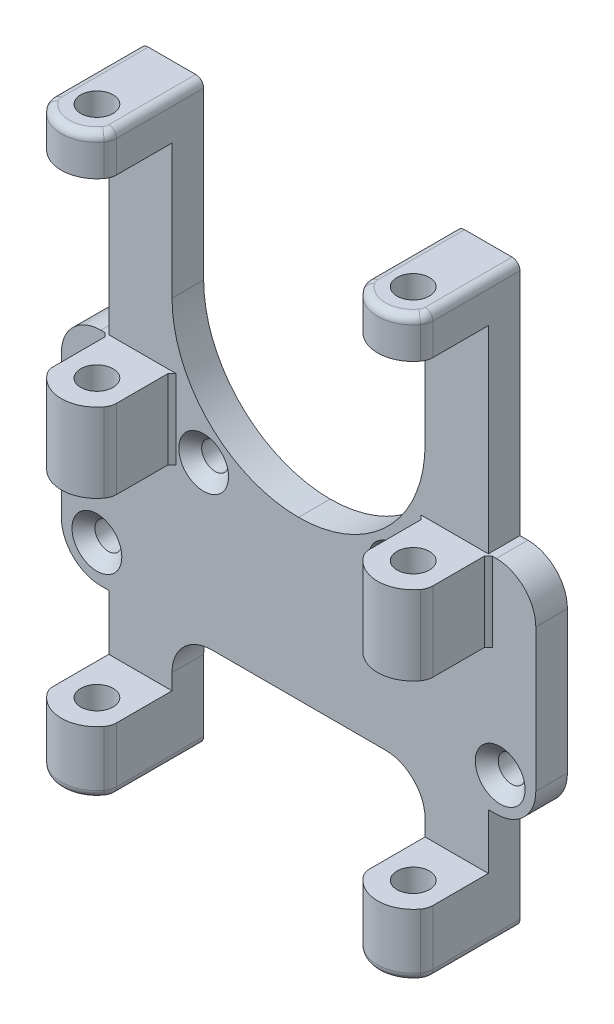
SolidWorks part; units mm, degrees
ref_plane "Front Plane" through (0, 0, 0) normal (0, 0, 1) x (1, 0, 0)
ref_plane "Top Plane" through (0, 0, 0) normal (0, 1, 0) x (1, 0, 0)
ref_plane "Right Plane" through (0, 0, 0) normal (1, 0, 0) x (0, 0, -1)
sketch "Sketch1" plane through (0, 0, 0) normal (0, 0, 1) x (1, 0, 0)
  line L0 (-30, 14) -> (30, -14) construction
  line L1 (-30, 14) -> (-16, 14)
  line L2 (-30, 14) -> (-30, -14)
  line L3 (-30, -14) -> (30, -14)
  line L4 (30, 14) -> (30, -14)
  line L5 (0, 0) -> (0, 36.8289) construction
  line L7 (16, 14) -> (30, 14)
  arc A3 (-16, 14) -> (16, 14) centre (0, 26) ccw
  point P4 (0, 0)
  point P5 (0, 0)
  point P8 (0, 6)
  dimension "D3" = 14
  dimension "D4" = 32
  dimension "D1" = 60
  dimension "D2" = 28
  dimension "D5" = 8
  dimension "D6" = 20
extrude "Boss-Extrude1" add sketch "Sketch1" along normal mid plane 4
sketch "Sketch2" plane through (0, 0, -2) normal (0, 0, -1) x (-1, 0, 0)
  line L5 (0, 0) -> (0, 55.0176) construction
  line L6 (16, 14) -> (30, 14) construction
  line L11 (-24, 44) -> (-16, 44)
  line L12 (-24, 44) -> (-24, -29)
  line L13 (-24, -29) -> (-16, -29)
  line L14 (-16, 44) -> (-16, -29)
  line L15 (16, 44) -> (24, 44)
  line L16 (16, 44) -> (16, -29)
  line L17 (16, -29) -> (24, -29)
  line L18 (24, 44) -> (24, -29)
  dimension "D1" = 48
  dimension "D2" = 8
  dimension "D3" = 73
  dimension "D4" = 30
extrude "Boss-Extrude2" add sketch "Sketch2" against normal up to surface (4 mm away) up to face at (0, 3.3333, 2)
hole_wizard "CSK for M3 Flat Countersunk Head Screw1" positions "Sketch3" profile "Sketch4" countersink size "M3" standard "JIS"
sketch "Sketch3" plane through (0, 0, 2) normal (0, 0, 1) x (1, 0, 0)
  line L1 (0, 0) -> (0, -19.5907) construction
  line L4 (30, -14) -> (30, 14) construction
  line L5 (24, -14) -> (30, -14) construction
  line L7 (30, 14) -> (24, 14) construction
  point P2 (25.5, -9.5)
  point P4 (-25.5, -9.5)
  point P25 (-12, 6)
  point P27 (12, 6)
  point P32 (0, 0)
  dimension "D2" = 4.5
  dimension "D3" = 4.5
  dimension "D4" = 8
  dimension "D5" = 24
sketch "Sketch4" plane through (25.5, -9.5, 2) normal (1, 0, 0) x (0, -1, 0)
  line L0 (0, 0) -> (0, 11.0215)
  line L1 (0, 11.0215) -> (1.7, 10)
  line L2 (1.7, 10) -> (1.7, 1.45)
  line L3 (1.7, 1.45) -> (3.15, 0)
  line L5 (3.15, 0) -> (0, 0)
  line L6 (-1.7, 1.45) -> (-3.15, 0) construction
  line L10 (0, 11.0215) -> (-1.7, 10) construction
  line L11 (0, -6.35) -> (0, 107.95) construction
  dimension "Hole Dia." = 3.4
  dimension "Hole Depth" = 10
  dimension "Near C'Sink Dia." = 6.3
  dimension "Near C'Sink Angle" = 90
  dimension "Drill Angle" = 118
sketch "Sketch5" plane through (0, -29, 0) normal (0, -1, 0) x (-1, 0, 0)
  line L0 (0, 0) -> (0, -18.7503) construction
  line L1 (-16, -2) -> (-24, -2) construction
  line L2 (24, -2) -> (24, -9.5616)
  line L3 (24, -2) -> (16, -2)
  line L4 (24, -2) -> (16, -2) construction
  line L5 (16, -2) -> (16, -9.5616)
  line L6 (-16, -9.5616) -> (-16, -2)
  line L7 (-16, -2) -> (-24, -2)
  line L8 (-24, -2) -> (-24, -9.5616)
  line L9 (-20, -7.5) -> (-20, -16.0423) construction
  circle A1 centre (20, -7.5) radius 2.05
  circle A2 centre (-20, -7.5) radius 2.05
  arc A3 (-24, -9.5616) -> (-16, -9.5616) centre (-20, -7.5) ccw
  arc A4 (16, -9.5616) -> (24, -9.5616) centre (20, -7.5) ccw
  dimension "D1" = 40
  dimension "D2" = 9
  dimension "D3" = 4.1
  dimension "D4" = 5.5
extrude "Boss-Extrude3" add sketch "Sketch5" against normal blind 8
sketch "Sketch6" plane through (0, 14, 0) normal (0, 1, 0) x (1, 0, 0)
  line L3 (24, -2) -> (16, -2)
  line L4 (24, -9.5616) -> (24, -2)
  line L5 (16, -2) -> (16, -9.5616)
  line L6 (24, -2) -> (16, -2)
  line L7 (24, -9.5616) -> (24, -2)
  line L8 (16, -2) -> (16, -9.5616)
  line L9 (-24, -2) -> (-24, -9.5616)
  line L10 (-16, -2) -> (-24, -2)
  line L11 (-16, -9.5616) -> (-16, -2)
  line L12 (-24, -2) -> (-24, -9.5616)
  line L13 (-16, -2) -> (-24, -2)
  line L14 (-16, -9.5616) -> (-16, -2)
  circle A1 centre (20, -7.5) radius 2.05
  circle A2 centre (20, -7.5) radius 2.05
  circle A3 centre (-20, -7.5) radius 2.05
  circle A4 centre (-20, -7.5) radius 2.05
  arc A5 (16, -9.5616) -> (24, -9.5616) centre (20, -7.5) ccw
  arc A7 (-24, -9.5616) -> (-16, -9.5616) centre (-20, -7.5) ccw
  arc A11 (16, -9.5616) -> (24, -9.5616) centre (20, -7.5) ccw construction
  arc A16 (16, -9.5616) -> (24, -9.5616) centre (20, -7.5) ccw
  arc A17 (-24, -9.5616) -> (-16, -9.5616) centre (-20, -7.5) ccw construction
  arc A18 (-24, -9.5616) -> (-16, -9.5616) centre (-20, -7.5) ccw
  dimension "D1" = 0
  dimension "D2" = 0
  dimension "D3" = 0
  dimension "D4" = 0
extrude "Boss-Extrude4" add sketch "Sketch6" against normal blind 10
sketch "Sketch7" plane through (0, 44, 0) normal (0, 1, 0) x (1, 0, 0)
  line L3 (24, -2) -> (16, -2)
  line L4 (24, -9.5616) -> (24, -2)
  line L5 (16, -2) -> (16, -9.5616)
  line L6 (24, -2) -> (16, -2)
  line L7 (24, -9.5616) -> (24, -2)
  line L8 (16, -2) -> (16, -9.5616)
  line L9 (-24, -2) -> (-24, -9.5616)
  line L10 (-16, -2) -> (-24, -2)
  line L11 (-16, -9.5616) -> (-16, -2)
  line L12 (-24, -2) -> (-24, -9.5616)
  line L13 (-16, -2) -> (-24, -2)
  line L14 (-16, -9.5616) -> (-16, -2)
  circle A1 centre (20, -7.5) radius 2.05
  circle A2 centre (20, -7.5) radius 2.05
  circle A3 centre (-20, -7.5) radius 2.05
  circle A4 centre (-20, -7.5) radius 2.05
  arc A5 (16, -9.5616) -> (24, -9.5616) centre (20, -7.5) ccw
  arc A6 (16, -9.5616) -> (24, -9.5616) centre (20, -7.5) ccw
  arc A7 (-24, -9.5616) -> (-16, -9.5616) centre (-20, -7.5) ccw
  arc A9 (-24, -9.5616) -> (-16, -9.5616) centre (-20, -7.5) ccw
  dimension "D1" = 0
  dimension "D2" = 0
  dimension "D3" = 0
  dimension "D4" = 0
extrude "Boss-Extrude5" add sketch "Sketch7" against normal blind 5
hole_wizard "CSK for M3 Flat Countersunk Head Screw2" positions "Sketch11" profile "Sketch12" countersink size "M3" standard "JIS" end condition up to next
sketch "Sketch11" plane through (0, 0, -2) normal (0, 0, -1) x (-1, 0, 0)
  line L2 (0, 0) -> (0, 26.2558) construction
  line L4 (24, 14) -> (30, 14) construction
  point P0 (-20, 9)
  point P2 (20, 9)
  dimension "D1" = 40
  dimension "D2" = 5
sketch "Sketch12" plane through (20, 9, -2) normal (1, 0, 0) x (0, 1, 0)
  line L0 (0, 0) -> (0, 7.45)
  line L1 (0, 7.45) -> (1.7, 7.45)
  line L2 (1.7, 7.45) -> (1.7, 2.45)
  line L3 (1.7, 2.45) -> (4.15, 0)
  line L5 (4.15, 0) -> (0, 0)
  line L6 (-1.7, 2.45) -> (-4.15, 0) construction
  line L11 (0, -6.35) -> (0, 107.95) construction
  dimension "Thru Hole Dia." = 3.4
  dimension "Thru Hole Depth" = 7.45
  dimension "Near C'Sink Dia." = 8.3
  dimension "Near C'Sink Angle" = 90
sketch "Sketch13" plane through (0, 0, -2) normal (0, 0, -1) x (-1, 0, 0)
  circle A0 centre (-20, 9) radius 2.1
  circle A1 centre (20, 9) radius 2.1
  dimension "D1" = 4.2
extrude "Cut-Extrude1" cut sketch "Sketch13" against normal blind 5
fillet "Fillet1" radius 5 6 edges at (30, -14, 0) (-30, -14, 0) (-30, 14, 0) (30, 14, 0) (16, -14, 0) (-16, -14, 0)
fillet "Fillet2" radius 16 2 edges at (16, 14, 0) (-16, 14, 0)
fillet "Fillet3" radius 2 12 edges at (16, -25, 9.5616) (24, -25, 9.5616) (-24, 41.5, 9.5616) (-16, 41.5, 9.5616) (24, 41.5, 9.5616) (16, 41.5, 9.5616) (16, 9, 9.5616) (24, 9, 9.5616) (-16, 9, 9.5616) (-24, 9, 9.5616) (-24, -25, 9.5616) (-16, -25, 9.5616)
fillet "Fillet4" radius 1 20 edges at (16, -29, 3.5) (-16, -29, 3.5) (16, 44, 3.5) (-16, 44, 3.5) (24, 44, 3.5) (-24, 44, 3.5) (-24, -29, 3.5) (24, -29, 3.5) (23.8974, -29, 9.6325) (20, -29, 12) (16.1026, -29, 9.6325) (-23.8974, -29, 9.6325) (-20, -29, 12) (-16.1026, -29, 9.6325) (23.8974, 44, 9.6325) (20, 44, 12) (16.1026, 44, 9.6325) (-23.8974, 44, 9.6325) (-20, 44, 12) (-16.1026, 44, 9.6325)
chamfer "Chamfer1" distance 0.5 angle 45 4 edges at (24, 9, 2) (16, 9, 2) (-24, 9, 2) (-16, 9, 2)
